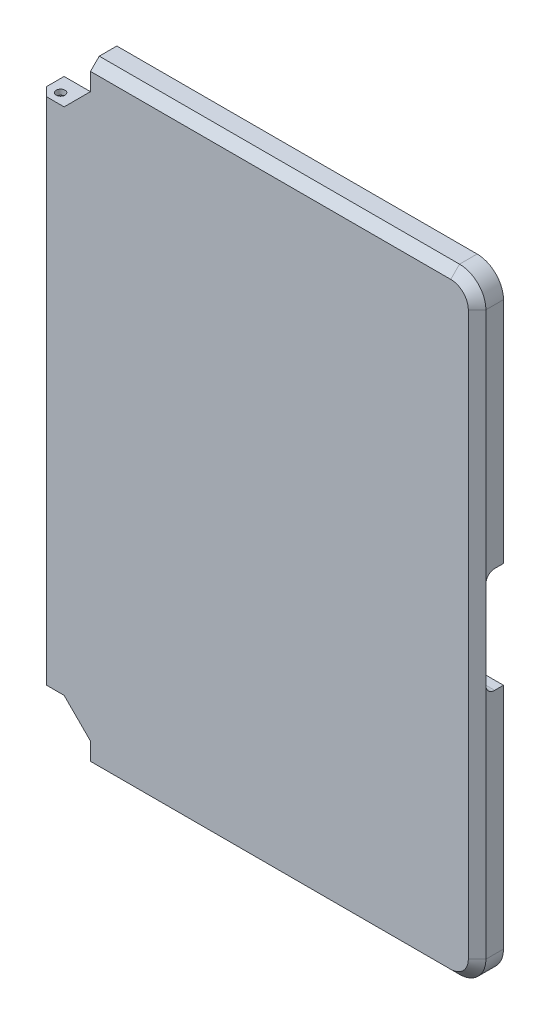
SolidWorks part; units mm, degrees
ref_plane "Front Plane" through (0, 0, 0) normal (0, 0, 1) x (1, 0, 0)
ref_plane "Top Plane" through (0, 0, 0) normal (0, 1, 0) x (1, 0, 0)
ref_plane "Right Plane" through (0, 0, 0) normal (1, 0, 0) x (0, 0, -1)
sketch "Sketch1" plane through (0, 0, 0) normal (0, 0, 1) x (1, 0, 0)
  line L1 (15, 0) -> (235, 0)
  line L2 (0, 15) -> (0, 335)
  line L3 (15, 350) -> (235, 350)
  line L4 (250, 15) -> (250, 335)
  arc A0 (0, 15) -> (15, 0) centre (15, 15) ccw
  arc A1 (235, 0) -> (250, 15) centre (235, 15) ccw
  arc A2 (250, 335) -> (235, 350) centre (235, 335) ccw
  arc A3 (15, 350) -> (0, 335) centre (15, 335) ccw
  point P7 (0, 0)
  point P10 (250, 0)
  point P15 (0, 350)
  dimension "D3" = 15
  dimension "D1" = 350
  dimension "D2" = 250
extrude "Boss-Extrude1" add sketch "Sketch1" along normal blind 15 contours L3 A2 L4 A1 L1 A0 L2 A3
chamfer "Chamfer1" distance 5 angle 45 8 edges at (125, 0, 15) (4.3934, 4.3934, 15) (245.6066, 4.3934, 15) (0, 175, 15) (250, 175, 15) (4.3934, 345.6066, 15) (245.6066, 345.6066, 15) (125, 350, 15)
sketch "Sketch2" plane through (0, 0, 15) normal (0, 0, 1) x (1, 0, 0)
  line L0 (0, 320) -> (15, 320)
  line L1 (0, 15) -> (0, 335) construction
  line L2 (15, 320) -> (30, 335)
  line L3 (30, 335) -> (30, 350)
  line L4 (15, 350) -> (235, 350) construction
  line L5 (30, 350) -> (0, 350)
  line L6 (0, 350) -> (0, 320)
  dimension "D1" = 15
  dimension "D2" = 15
  dimension "D3" = 45
  dimension "D4" = 30
extrude "Cut-Extrude1" cut sketch "Sketch2" against normal up to next
ref_plane "Plane1" through (0, 175, 0) normal (0, 1, 0) x (1, 0, 0)
mirror "Mirror1" about plane through (0, 175, 0) normal (0, 1, 0) of "Cut-Extrude1"
sketch "Sketch3" plane through (0, 0, 0) normal (0, 0, -1) x (-1, 0, 0)
  line L0 (-250, 15) -> (-250, 335) construction
  line L1 (-250, 205) -> (-240, 205)
  line L2 (-250, 205) -> (-250, 145)
  line L3 (-250, 145) -> (-240, 145)
  line L4 (-230, 195) -> (-230, 155)
  line L5 (0, 175) -> (-250, 175) construction
  line L6 (0, 30) -> (0, 320) construction
  arc A0 (-240, 145) -> (-230, 155) centre (-240, 155) ccw
  arc A1 (-230, 195) -> (-240, 205) centre (-240, 195) ccw
  point P10 (-245, 205)
  point P15 (-230, 205)
  dimension "D4" = 10
  dimension "D1" = 30
  dimension "D2" = 30
  dimension "D3" = 20
extrude "Cut-Extrude2" cut sketch "Sketch3" against normal blind 10 contours L4 A0 L3 L2 L1 A1
shell "Shell1" thickness 3 removed face at (142.3373, 175, 0)
sketch "Sketch4" plane through (0, 0, 12) normal (0, 0, -1) x (-1, 0, 0)
  line L0 (-250, 205) -> (-250, 335) construction
  line L1 (-217.5, 25) -> (-32.5, 25)
  line L2 (-222.5, 30) -> (-222.5, 320)
  line L3 (-217.5, 325) -> (-32.5, 325)
  line L4 (-27.5, 30) -> (-27.5, 320)
  line L5 (0, 30) -> (0, 320) construction
  line L6 (-30, 350) -> (-235, 350) construction
  line L7 (-30, 0) -> (-235, 0) construction
  line L8 (-217.5, 324) -> (-32.5, 324)
  line L9 (-28.5, 30) -> (-28.5, 320)
  line L10 (-217.5, 26) -> (-32.5, 26)
  line L11 (-221.5, 30) -> (-221.5, 320)
  line L12 (-217.5, 329) -> (-32.5, 329)
  line L13 (-23.5, 30) -> (-23.5, 320)
  line L14 (-217.5, 21) -> (-32.5, 21)
  line L15 (-226.5, 30) -> (-226.5, 320)
  line L16 (-229.5, 30) -> (-229.5, 320)
  line L17 (-217.5, 332) -> (-32.5, 332)
  line L18 (-20.5, 30) -> (-20.5, 320)
  line L19 (-217.5, 18) -> (-32.5, 18)
  line L20 (-217.5, 321) -> (-32.5, 321)
  line L21 (-31.5, 30) -> (-31.5, 320)
  line L22 (-217.5, 29) -> (-32.5, 29)
  line L23 (-218.5, 30) -> (-218.5, 320)
  arc A0 (-32.5, 25) -> (-27.5, 30) centre (-32.5, 30) ccw
  arc A1 (-27.5, 320) -> (-32.5, 325) centre (-32.5, 320) ccw
  arc A2 (-217.5, 325) -> (-222.5, 320) centre (-217.5, 320) ccw
  arc A3 (-222.5, 30) -> (-217.5, 25) centre (-217.5, 30) ccw
  arc A4 (-28.5, 320) -> (-32.5, 324) centre (-32.5, 320) ccw
  arc A5 (-32.5, 26) -> (-28.5, 30) centre (-32.5, 30) ccw
  arc A6 (-221.5, 30) -> (-217.5, 26) centre (-217.5, 30) ccw
  arc A7 (-217.5, 324) -> (-221.5, 320) centre (-217.5, 320) ccw
  arc A8 (-23.5, 320) -> (-32.5, 329) centre (-32.5, 320) ccw
  arc A9 (-32.5, 21) -> (-23.5, 30) centre (-32.5, 30) ccw
  arc A10 (-226.5, 30) -> (-217.5, 21) centre (-217.5, 30) ccw
  arc A11 (-217.5, 329) -> (-226.5, 320) centre (-217.5, 320) ccw
  arc A12 (-217.5, 332) -> (-229.5, 320) centre (-217.5, 320) ccw
  arc A13 (-20.5, 320) -> (-32.5, 332) centre (-32.5, 320) ccw
  arc A14 (-32.5, 18) -> (-20.5, 30) centre (-32.5, 30) ccw
  arc A15 (-229.5, 30) -> (-217.5, 18) centre (-217.5, 30) ccw
  arc A16 (-31.5, 320) -> (-32.5, 321) centre (-32.5, 320) ccw
  arc A17 (-32.5, 29) -> (-31.5, 30) centre (-32.5, 30) ccw
  arc A18 (-218.5, 30) -> (-217.5, 29) centre (-217.5, 30) ccw
  arc A19 (-217.5, 321) -> (-218.5, 320) centre (-217.5, 320) ccw
  arc M9 (-227, 155) -> (-240, 142) centre (-240, 155) cw
  line M15 (-33, 16.2426) -> (-16.2426, 33)
  line M19 (-16.2426, 317) -> (-33, 333.7574)
  arc M25 (-240, 208) -> (-227, 195) centre (-240, 195) cw
  line M26 (-227, 195) -> (-227, 155)
  dimension "D5" = 5
  dimension "D1" = 27.5
  dimension "D2" = 27.5
  dimension "D3" = 25
  dimension "D4" = 25
  dimension "D6" = 1
  dimension "D7" = 4
  dimension "D8" = 3
  dimension "D9" = 3
extrude "Boss-Extrude2" add sketch "Sketch4" along normal up to surface (12 mm away) contours L16 A15 L19 A14 L18 A13 L17 A12 A11 L12 A8 L13 A9 L14 A10 L15 M15 M19 M25 M26 M9 | L8 A7 L11 A6 L10 A5 L9 A4 A19 L20 A16 L21 A17 L22 A18 L23 region at (125, 323.645, 12) region at (229.1228, 88.6676, 12) up to face at (142.3373, 175, 0)
sketch "Sketch5" plane through (0, 320, 0) normal (0, 1, 0) x (1, 0, 0)
  line L0 (5, -15) -> (15, -15) construction
  line L1 (0, 0) -> (0, -10) construction
  circle A0 centre (7, -9) radius 2.5
  dimension "D1" = 5
  dimension "D2" = 6
  dimension "D3" = 7
extrude "Cut-Extrude3" cut sketch "Sketch5" against normal through all
fillet "Fillet1" radius 5 5 edges at (245, 145, 10) (232.9289, 147.9289, 10) (230, 175, 10) (245, 205, 10) (232.9289, 202.0711, 10)
